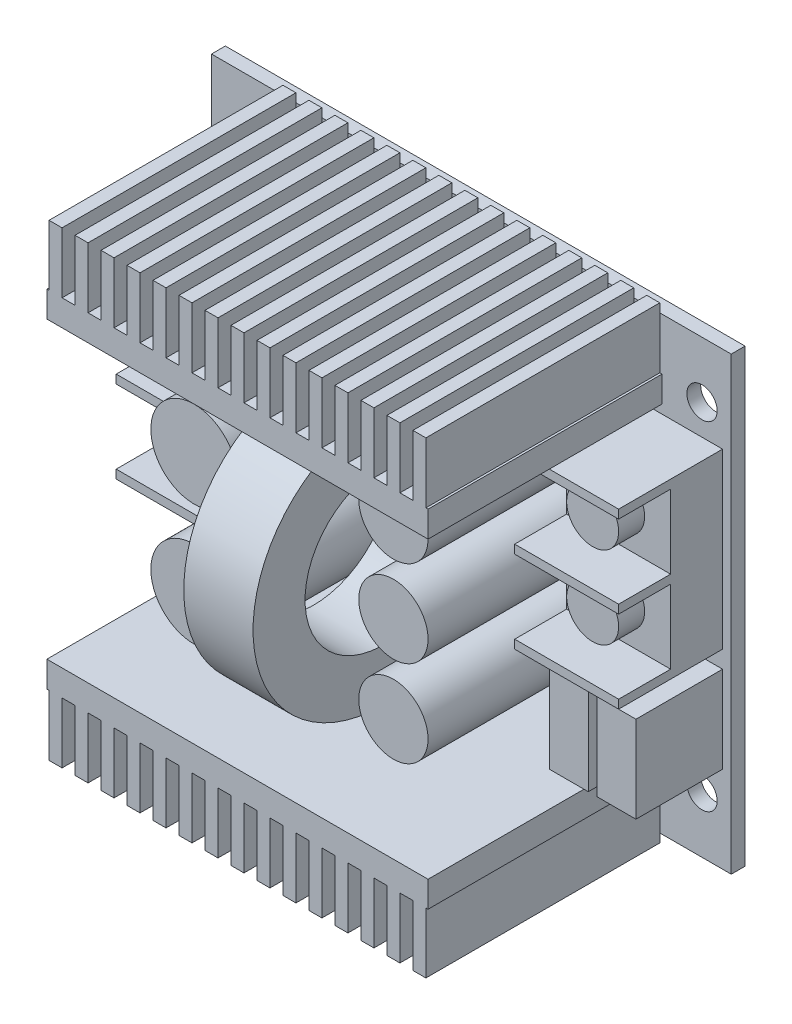
SolidWorks part; units mm, degrees
ref_plane "Top Plane" through (0, 0, 0) normal (0, 0, 1) x (1, 0, 0)
ref_plane "Right Plane" through (0, 0, 0) normal (0, 1, 0) x (1, 0, 0)
ref_plane "Front Plane" through (0, 0, 0) normal (1, 0, 0) x (0, 0, -1)
sketch "Sketch1" plane through (0, 0, 0) normal (0, 0, 1) x (1, 0, 0)
  line L0 (-30, 26) -> (30, -26) construction
  line L1 (-30, 26) -> (30, 26)
  line L2 (-30, 26) -> (-30, -26)
  line L3 (-30, -26) -> (30, -26)
  line L4 (30, 26) -> (30, -26)
  dimension "D1" = 60
  dimension "D2" = 52
extrude "Boss-Extrude1" add sketch "Sketch1" along normal mid plane 1.6
sketch "Sketch2" plane through (0, 0, 0.8) normal (0, 0, 1) x (1, 0, 0)
  line L0 (-30, 0) -> (30, 0) construction
  line L1 (-22, -27) -> (22, -27)
  line L2 (-22, -27) -> (-22, -17)
  line L3 (-22, -17) -> (22, -17)
  line L4 (22, -27) -> (22, -17)
  line L5 (-30, 26) -> (-30, -26) construction
  line L6 (30, -26) -> (30, 26) construction
  line L7 (22, 27) -> (22, 17)
  line L8 (-22, 17) -> (22, 17)
  line L9 (-22, 27) -> (-22, 17)
  line L10 (-22, 27) -> (22, 27)
  line L11 (0, -27) -> (0, 27) construction
  line L12 (-30, -26) -> (30, -26) construction
  dimension "D1" = 10
  dimension "D2" = 1
  dimension "D3" = 8
extrude "Boss-Extrude2" add sketch "Sketch2" along normal blind 27
sketch "Sketch3" plane through (0, 0, 27.8) normal (0, 0, 1) x (1, 0, 0)
  line L0 (-22, -27) -> (22, -27) construction
  line L1 (-23.25, -20) -> (-21.75, -20)
  line L2 (-23.25, -20) -> (-23.25, -27)
  line L3 (-23.25, -27) -> (-21.75, -27)
  line L4 (-21.75, -20) -> (-21.75, -27)
  line L5 (-20.25, -20) -> (-18.75, -20)
  line L6 (-20.25, -20) -> (-20.25, -27)
  line L7 (-20.25, -27) -> (-18.75, -27)
  line L8 (-18.75, -20) -> (-18.75, -27)
  line L9 (-17.25, -20) -> (-15.75, -20)
  line L10 (-17.25, -20) -> (-17.25, -27)
  line L11 (-17.25, -27) -> (-15.75, -27)
  line L12 (-15.75, -20) -> (-15.75, -27)
  line L13 (-14.25, -20) -> (-12.75, -20)
  line L14 (-14.25, -20) -> (-14.25, -27)
  line L15 (-14.25, -27) -> (-12.75, -27)
  line L16 (-12.75, -20) -> (-12.75, -27)
  line L17 (-11.25, -20) -> (-9.75, -20)
  line L18 (-11.25, -20) -> (-11.25, -27)
  line L19 (-11.25, -27) -> (-9.75, -27)
  line L20 (-9.75, -20) -> (-9.75, -27)
  line L21 (-8.25, -20) -> (-6.75, -20)
  line L22 (-8.25, -20) -> (-8.25, -27)
  line L23 (-8.25, -27) -> (-6.75, -27)
  line L24 (-6.75, -20) -> (-6.75, -27)
  line L25 (-5.25, -20) -> (-3.75, -20)
  line L26 (-5.25, -20) -> (-5.25, -27)
  line L27 (-5.25, -27) -> (-3.75, -27)
  line L28 (-3.75, -20) -> (-3.75, -27)
  line L29 (-2.25, -20) -> (-0.75, -20)
  line L30 (-2.25, -20) -> (-2.25, -27)
  line L31 (-2.25, -27) -> (-0.75, -27)
  line L32 (-0.75, -20) -> (-0.75, -27)
  line L33 (0.75, -20) -> (2.25, -20)
  line L34 (0.75, -20) -> (0.75, -27)
  line L35 (0.75, -27) -> (2.25, -27)
  line L36 (2.25, -20) -> (2.25, -27)
  line L37 (3.75, -20) -> (5.25, -20)
  line L38 (3.75, -20) -> (3.75, -27)
  line L39 (3.75, -27) -> (5.25, -27)
  line L40 (5.25, -20) -> (5.25, -27)
  line L41 (6.75, -20) -> (8.25, -20)
  line L42 (6.75, -20) -> (6.75, -27)
  line L43 (6.75, -27) -> (8.25, -27)
  line L44 (8.25, -20) -> (8.25, -27)
  line L45 (9.75, -20) -> (11.25, -20)
  line L46 (9.75, -20) -> (9.75, -27)
  line L47 (9.75, -27) -> (11.25, -27)
  line L48 (11.25, -20) -> (11.25, -27)
  line L49 (12.75, -20) -> (14.25, -20)
  line L50 (12.75, -20) -> (12.75, -27)
  line L51 (12.75, -27) -> (14.25, -27)
  line L52 (14.25, -20) -> (14.25, -27)
  line L53 (15.75, -20) -> (17.25, -20)
  line L54 (15.75, -20) -> (15.75, -27)
  line L55 (15.75, -27) -> (17.25, -27)
  line L56 (17.25, -20) -> (17.25, -27)
  line L57 (18.75, -20) -> (20.25, -20)
  line L58 (18.75, -20) -> (18.75, -27)
  line L59 (18.75, -27) -> (20.25, -27)
  line L60 (20.25, -20) -> (20.25, -27)
  line L61 (21.75, -20) -> (23.25, -20)
  line L62 (21.75, -20) -> (21.75, -27)
  line L63 (21.75, -27) -> (23.25, -27)
  line L64 (23.25, -20) -> (23.25, -27)
  line L65 (-23.25, -20) -> (-20.25, -20) construction
  line L66 (-22, -22.7057) -> (-23.25, -22.7057) construction
  line L67 (-22, -17) -> (-22, -26) construction
  line L68 (23.25, -22.7057) -> (22, -22.7057) construction
  line L69 (22, -27) -> (22, -17) construction
  line L70 (22, -17) -> (-22, -17) construction
  line L71 (-38.482, 0) -> (38.482, 0) construction
  line L72 (23.25, 20) -> (23.25, 27)
  line L73 (21.75, 27) -> (23.25, 27)
  line L74 (21.75, 20) -> (21.75, 27)
  line L75 (21.75, 20) -> (23.25, 20)
  line L76 (20.25, 20) -> (20.25, 27)
  line L77 (18.75, 27) -> (20.25, 27)
  line L78 (18.75, 20) -> (18.75, 27)
  line L79 (18.75, 20) -> (20.25, 20)
  line L80 (17.25, 20) -> (17.25, 27)
  line L81 (15.75, 27) -> (17.25, 27)
  line L82 (15.75, 20) -> (15.75, 27)
  line L83 (15.75, 20) -> (17.25, 20)
  line L84 (14.25, 20) -> (14.25, 27)
  line L85 (12.75, 27) -> (14.25, 27)
  line L86 (12.75, 20) -> (12.75, 27)
  line L87 (12.75, 20) -> (14.25, 20)
  line L88 (11.25, 20) -> (11.25, 27)
  line L89 (9.75, 27) -> (11.25, 27)
  line L90 (9.75, 20) -> (9.75, 27)
  line L91 (9.75, 20) -> (11.25, 20)
  line L92 (8.25, 20) -> (8.25, 27)
  line L93 (6.75, 27) -> (8.25, 27)
  line L94 (6.75, 20) -> (6.75, 27)
  line L95 (6.75, 20) -> (8.25, 20)
  line L96 (5.25, 20) -> (5.25, 27)
  line L97 (3.75, 27) -> (5.25, 27)
  line L98 (3.75, 20) -> (3.75, 27)
  line L99 (3.75, 20) -> (5.25, 20)
  line L100 (2.25, 20) -> (2.25, 27)
  line L101 (0.75, 27) -> (2.25, 27)
  line L102 (0.75, 20) -> (0.75, 27)
  line L103 (0.75, 20) -> (2.25, 20)
  line L104 (-0.75, 20) -> (-0.75, 27)
  line L105 (-2.25, 27) -> (-0.75, 27)
  line L106 (-2.25, 20) -> (-2.25, 27)
  line L107 (-2.25, 20) -> (-0.75, 20)
  line L108 (-3.75, 20) -> (-3.75, 27)
  line L109 (-5.25, 27) -> (-3.75, 27)
  line L110 (-5.25, 20) -> (-5.25, 27)
  line L111 (-5.25, 20) -> (-3.75, 20)
  line L112 (-6.75, 20) -> (-6.75, 27)
  line L113 (-8.25, 27) -> (-6.75, 27)
  line L114 (-8.25, 20) -> (-8.25, 27)
  line L115 (-8.25, 20) -> (-6.75, 20)
  line L116 (-9.75, 20) -> (-9.75, 27)
  line L117 (-11.25, 27) -> (-9.75, 27)
  line L118 (-11.25, 20) -> (-11.25, 27)
  line L119 (-11.25, 20) -> (-9.75, 20)
  line L120 (-12.75, 20) -> (-12.75, 27)
  line L121 (-14.25, 27) -> (-12.75, 27)
  line L122 (-14.25, 20) -> (-14.25, 27)
  line L123 (-14.25, 20) -> (-12.75, 20)
  line L124 (-15.75, 20) -> (-15.75, 27)
  line L125 (-17.25, 27) -> (-15.75, 27)
  line L126 (-17.25, 20) -> (-17.25, 27)
  line L127 (-17.25, 20) -> (-15.75, 20)
  line L128 (-18.75, 20) -> (-18.75, 27)
  line L129 (-20.25, 27) -> (-18.75, 27)
  line L130 (-20.25, 20) -> (-20.25, 27)
  line L131 (-20.25, 20) -> (-18.75, 20)
  line L132 (-21.75, 20) -> (-21.75, 27)
  line L133 (-23.25, 27) -> (-21.75, 27)
  line L134 (-23.25, 20) -> (-23.25, 27)
  line L135 (-23.25, 20) -> (-21.75, 20)
  dimension "D1" = 16
  dimension "D2" = 3
  dimension "D3" = 1.5
  dimension "D4" = 3
extrude "Cut-Extrude1" cut sketch "Sketch3" against normal up to surface (27 mm away) up to face at (0, 0, 0.8)
sketch "Sketch4" plane through (0, 0, 0.8) normal (0, 0, 1) x (1, 0, 0)
  line L0 (-30, 0) -> (30, 0) construction
  line L1 (-30, 26) -> (-30, -26) construction
  line L2 (30, -26) -> (30, 26) construction
  line L3 (0, -30.646) -> (0, 35.9865) construction
  circle A0 centre (-26.625, -19.5) radius 1.75
  circle A1 centre (-26.625, 19.5) radius 1.75
  circle A2 centre (26.625, 19.5) radius 1.75
  circle A3 centre (26.625, -19.5) radius 1.75
  dimension "D1" = 39
  dimension "D3" = 3.5
  dimension "D2" = 53.25
extrude "Cut-Extrude2" cut sketch "Sketch4" against normal through all
sketch "Sketch5" plane through (0, 0, 0.8) normal (0, 0, 1) x (1, 0, 0)
  line L0 (24, -1.5528) -> (24, -15.2326) construction
  line L1 (19, -6) -> (23.5, -6)
  line L2 (19, -6) -> (19, -16)
  line L3 (19, -16) -> (23.5, -16)
  line L4 (23.5, -6) -> (23.5, -16)
  line L5 (24.5, -6) -> (24.5, -16)
  line L6 (29, -16) -> (24.5, -16)
  line L7 (29, -6) -> (29, -16)
  line L8 (29, -6) -> (24.5, -6)
  line L9 (30, -26) -> (30, 26) construction
  line L10 (22, -17) -> (-22, -17) construction
  dimension "D1" = 1
  dimension "D2" = 10
  dimension "D3" = 10
  dimension "D4" = 1
  dimension "D5" = 1
extrude "Boss-Extrude3" add sketch "Sketch5" along normal blind 10
sketch "Sketch6" plane through (0, 0, 0.8) normal (0, 0, 1) x (1, 0, 0)
  line L0 (30, -26) -> (30, 26) construction
  line L1 (17, 16) -> (29, 16)
  line L2 (17, 16) -> (17, -4)
  line L3 (17, -4) -> (29, -4)
  line L4 (29, 16) -> (29, -4)
  line L5 (29, -6) -> (24.5, -6) construction
  line L6 (-22, 17) -> (22, 17) construction
  line L7 (-30, 0) -> (-17, 0) construction
  line L8 (-29, -10) -> (-17, -10)
  line L9 (-29, -10) -> (-29, 10)
  line L10 (-29, 10) -> (-17, 10)
  line L11 (-17, -10) -> (-17, 10)
  line L12 (-30, 26) -> (-30, -26) construction
  dimension "D1" = 1
  dimension "D2" = 2
  dimension "D3" = 1
  dimension "D4" = 12
  dimension "D5" = 1
extrude "Boss-Extrude4" add sketch "Sketch6" along normal blind 12
sketch "Sketch7" plane through (0, 0, 12.8) normal (0, 0, 1) x (1, 0, 0)
  line L0 (17, 16) -> (17, -4) construction
  line L1 (17, 15) -> (29, 15)
  line L2 (17, 15) -> (17, 6.5)
  line L3 (17, 6.5) -> (29, 6.5)
  line L4 (29, 15) -> (29, 6.5)
  line L5 (29, -4) -> (29, 16) construction
  line L6 (17, 6) -> (29, 6) construction
  line L7 (17, 16) -> (17, -4) construction
  line L8 (29, -4) -> (29, 16) construction
  line L9 (29, -3) -> (29, 5.5)
  line L10 (17, 5.5) -> (29, 5.5)
  line L11 (17, -3) -> (17, 5.5)
  line L12 (17, -3) -> (29, -3)
  line L13 (17, -4) -> (29, -4) construction
  line L14 (-29, 9) -> (-17, 9)
  line L15 (-29, 9) -> (-29, 0.5)
  line L16 (-29, 0.5) -> (-17, 0.5)
  line L17 (-17, 9) -> (-17, 0.5)
  line L18 (-29, 0) -> (-17, 0) construction
  line L19 (-17, -9) -> (-17, -0.5)
  line L20 (-29, -0.5) -> (-17, -0.5)
  line L21 (-29, -9) -> (-29, -0.5)
  line L22 (-29, -9) -> (-17, -9)
  line L23 (-29, 10) -> (-29, -10) construction
  line L24 (-17, -10) -> (-17, 10) construction
  dimension "D1" = 1
  dimension "D2" = 1
  dimension "D3" = 1
extrude "Cut-Extrude3" cut sketch "Sketch7" against normal offset from surface (6 mm away) 6 up to face at (-28.375, 19.5, 0.8)
sketch "Sketch8" plane through (0, 0, 6.8) normal (0, 0, 1) x (1, 0, 0)
  line L0 (17, 10.75) -> (29, 10.75) construction
  line L1 (17, 6.5) -> (17, 15) construction
  line L2 (29, 15) -> (29, 6.5) construction
  line L3 (17, 1.25) -> (29, 1.25) construction
  line L4 (17, -3) -> (17, 5.5) construction
  line L5 (29, 5.5) -> (29, -3) construction
  line L6 (-29, 4.75) -> (-17, 4.75) construction
  line L7 (-29, -4.75) -> (-17, -4.75) construction
  line L8 (-29, -9) -> (-29, -0.5) construction
  line L9 (-17, -10) -> (-17, 10) construction
  line L10 (-29, 0.5) -> (-29, 9) construction
  line L11 (-17, 9) -> (-17, 0.5) construction
  circle A0 centre (23, 10.75) radius 3
  circle A1 centre (23, 1.25) radius 3
  circle A2 centre (-23, 4.75) radius 3
  circle A3 centre (-23, -4.75) radius 3
  dimension "D1" = 6
extrude "Boss-Extrude5" add sketch "Sketch8" along normal blind 3
sketch "Sketch9" plane through (0, 0, 0.8) normal (0, 0, 1) x (1, 0, 0)
  line L0 (-31.7963, 0) -> (33.7681, 0) construction
  line L1 (22, -17) -> (-22, -17) construction
  circle A0 centre (11, 0) radius 4
  circle A1 centre (11, -10) radius 4
  circle A2 centre (11, 10) radius 4
  dimension "D1" = 8
  dimension "D2" = 7
  dimension "D3" = 11
extrude "Boss-Extrude6" add sketch "Sketch9" along normal blind 20
sketch "Sketch10" plane through (0, 0, 0.8) normal (0, 0, 1) x (1, 0, 0)
  line L0 (-34.1614, 0) -> (43.5559, 0) construction
  circle A0 centre (-10, 7) radius 5
  circle A1 centre (-10, -7) radius 5
  dimension "D1" = 10
  dimension "D2" = 10
  dimension "D3" = 14
extrude "Boss-Extrude7" add sketch "Sketch10" along normal blind 22
sketch "Sketch11" plane through (0, 0, 0) normal (1, 0, 0) x (0, 0, -1)
  line L0 (-15, 0) -> (0, 0) construction
  circle A0 centre (-15, 0) radius 15
  circle A1 centre (-15, 0) radius 9
  dimension "D1" = 30
  dimension "D2" = 6
extrude "Boss-Extrude8" add sketch "Sketch11" along normal mid plane 8
